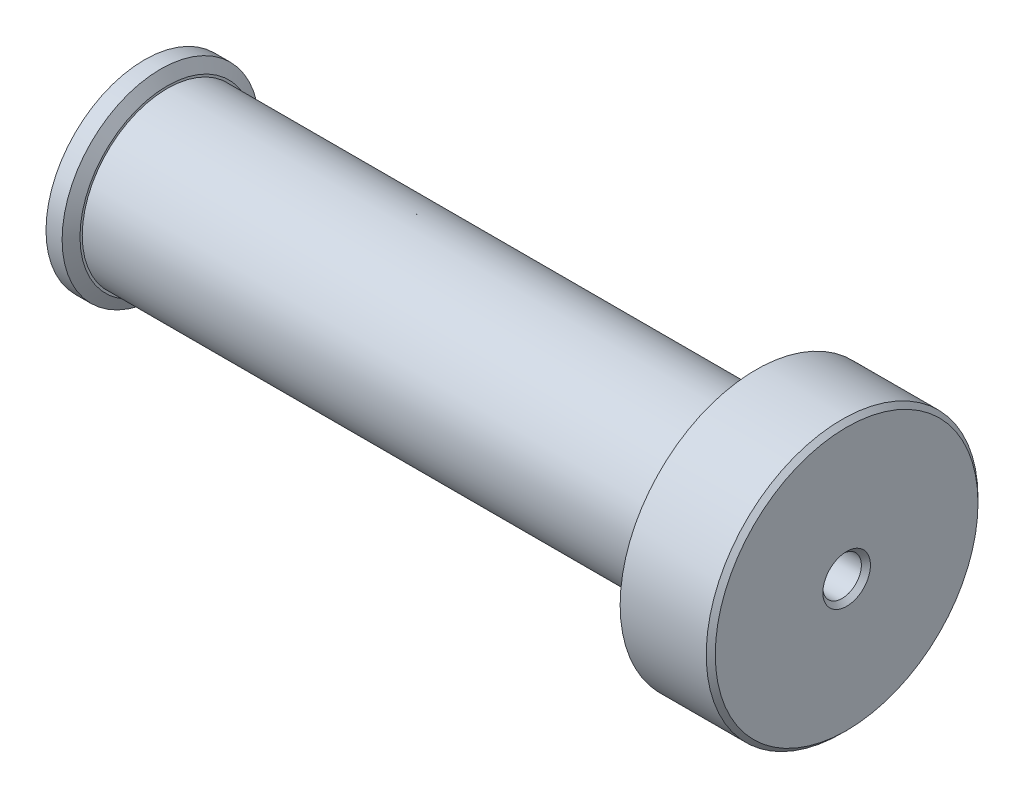
SolidWorks part; units mm, degrees
material "Custom Plastic"
ref_plane "Front Plane" through (0, 0, 0) normal (0, 0, 1) x (1, 0, 0)
ref_plane "Top Plane" through (0, 0, 0) normal (0, 1, 0) x (1, 0, 0)
ref_plane "Right Plane" through (0, 0, 0) normal (1, 0, 0) x (0, 0, -1)
sketch "Sketch3" plane through (0, 0, 0) normal (0, 1, 0) x (1, 0, 0)
  line L0 (0, 0) -> (-62, 0) construction
  line L1 (-62, 0) -> (-62, 8.7)
  line L2 (-62, 8.7) -> (-60, 8.7)
  line L3 (-60, 8.7) -> (-60, 7.5)
  line L4 (-60, 7.5) -> (-10, 7.5)
  line L5 (-10, 7.5) -> (-10, 12)
  line L6 (-10, 12) -> (0, 12)
  line L7 (0, 12) -> (0, 0)
  line L8 (0, 0) -> (-62, 0)
  dimension "D1" = 24
  dimension "D2" = 15
  dimension "D3" = 10
  dimension "D4" = 50
  dimension "D5" = 2
  dimension "D6" = 1.2
revolve "Revolve1" add sketch "Sketch3" angle 360 about L0
chamfer "Chamfer1" distance 1 angle 30 1 edges at (-60, 0, -8.7) first distance on face at (-60, 0, -8.7)
chamfer "Chamfer2" distance 2 angle 60 1 edges at (-10, 0, -12) first distance on face at (-10, 0, -12)
sketch "Sketch4" plane through (-62, 0, 0) normal (-1, 0, 0) x (0, 0, 1)
  circle A0 centre (0, 0) radius 6.3
  circle A1 centre (0, 0) radius 7.5 construction
  dimension "D1" = 1.2
extrude "Cut-Extrude1" cut sketch "Sketch4" against normal offset from surface (53 mm away) 9 up to face at (0, 0, -12)
sketch "Sketch5" plane through (-9, 0, 0) normal (-1, 0, 0) x (0, 0, 1)
  circle A0 centre (0, 0) radius 1.7
  dimension "D1" = 3.4
extrude "Cut-Extrude2" cut sketch "Sketch5" against normal through all
chamfer "Chamfer3" distance 0.4 angle 45 2 edges at (0, 0, -12) (0, 0, 1.7)
